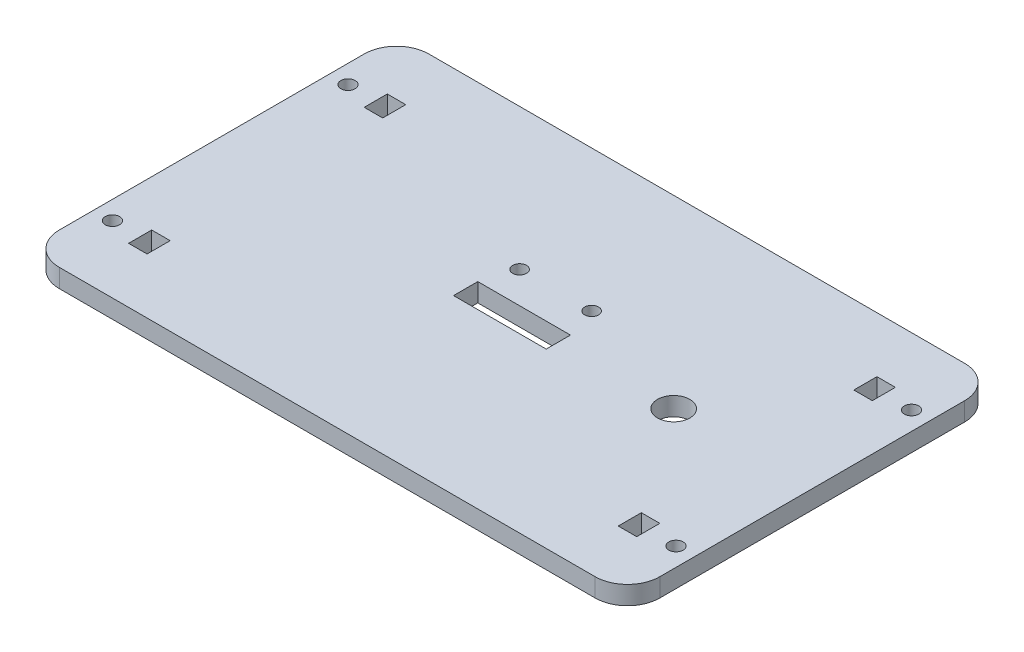
SolidWorks part; units mm, degrees
ref_plane "Front Plane" through (0, 0, 0) normal (0, 0, 1) x (1, 0, 0)
ref_plane "Top Plane" through (0, 0, 0) normal (0, 1, 0) x (1, 0, 0)
ref_plane "Right Plane" through (0, 0, 0) normal (1, 0, 0) x (0, 0, -1)
sketch "Sketch1" plane through (0, 0, 0) normal (0, 1, 0) x (1, 0, 0)
  line L0 (0, 0) -> (0, 18.9717) construction
  line L1 (-58, -40) -> (58, -40)
  line L2 (-65, -33) -> (-65, 33)
  line L3 (-58, 40) -> (58, 40)
  line L4 (65, -33) -> (65, 33)
  line L5 (-65, -40) -> (65, 40) construction
  line L6 (-65, 40) -> (65, -40) construction
  line L11 (0, 0) -> (21.4077, 0) construction
  line L30 (51, -23) -> (55, -23)
  line L31 (51, -23) -> (51, -28)
  line L32 (51, -28) -> (55, -28)
  line L33 (55, -23) -> (55, -28)
  line L34 (51, -23) -> (55, -28) construction
  line L35 (51, -28) -> (55, -23) construction
  line L36 (51, 28) -> (55, 28)
  line L37 (51, 28) -> (51, 23)
  line L38 (51, 23) -> (55, 23)
  line L39 (55, 28) -> (55, 23)
  line L40 (51, 28) -> (55, 23) construction
  line L41 (51, 23) -> (55, 28) construction
  line L42 (-55, 28) -> (-51, 28)
  line L43 (-55, 28) -> (-55, 23)
  line L44 (-55, 23) -> (-51, 23)
  line L45 (-51, 28) -> (-51, 23)
  line L46 (-55, 28) -> (-51, 23) construction
  line L47 (-55, 23) -> (-51, 28) construction
  line L48 (-55, -23) -> (-51, -23)
  line L49 (-55, -23) -> (-55, -28)
  line L50 (-55, -28) -> (-51, -28)
  line L51 (-51, -23) -> (-51, -28)
  line L52 (-55, -23) -> (-51, -28) construction
  line L53 (-55, -28) -> (-51, -23) construction
  line L54 (-10.03, 2.625) -> (10.03, 2.625)
  line L55 (-10.03, 2.625) -> (-10.03, -2.625)
  line L56 (-10.03, -2.625) -> (10.03, -2.625)
  line L57 (10.03, 2.625) -> (10.03, -2.625)
  line L58 (-10.03, 2.625) -> (10.03, -2.625) construction
  line L59 (-10.03, -2.625) -> (10.03, 2.625) construction
  circle A0 centre (61, 25.5) radius 1.55
  circle A1 centre (61, -25.5) radius 1.55
  circle A2 centre (-61, -25.5) radius 1.55
  circle A3 centre (-61, 25.5) radius 1.55
  circle A8 centre (35, 0) radius 3.5
  arc A9 (58, 40) -> (65, 33) centre (58, 33) cw
  arc A10 (58, -40) -> (65, -33) centre (58, -33) ccw
  arc A11 (-58, -40) -> (-65, -33) centre (-58, -33) cw
  arc A12 (-65, 33) -> (-58, 40) centre (-58, 33) cw
  circle A13 centre (-7.8, 9.445) radius 1.5
  circle A14 centre (7.8, 9.445) radius 1.5
  point P0 (0, 0)
  point P6 (53, 25.5)
  point P14 (-53, 25.5)
  point P19 (-53, -25.5)
  point P24 (0, 0)
  point P62 (53, -25.5)
  point P75 (-10.9239, 16.3216)
  point P76 (-8.6491, 16.0183)
  point P77 (-12.3899, 13.4402)
  point P78 (8.7908, 16.3216)
  point P79 (11.2678, 13.4402)
  point P80 (0, 0)
  point P81 (-12.2382, 16.3722)
  point P82 (-5.1, 9.445)
  point P83 (-6.9809, 9.445)
  point P84 (-12.3393, 10.5588)
  dimension "D8" = 3.1
  dimension "D12" = 7
  dimension "D13" = 7
  dimension "D3" = 4
  dimension "D27" = 3
  dimension "D1" = 80
  dimension "D2" = 130
  dimension "D4" = 10
  dimension "D5" = 12
  dimension "D6" = 4
  dimension "D7" = 14.5
  dimension "D9" = 54.97
  dimension "D10" = 54.97
  dimension "D11" = 35
  dimension "D14" = 4
  dimension "D15" = 5
  dimension "D16" = 10
  dimension "D17" = 12
  dimension "D18" = 5
  dimension "D19" = 12
  dimension "D20" = 10
  dimension "D21" = 12
  dimension "D22" = 10
  dimension "D23" = 37.375
  dimension "D24" = 20.06
  dimension "D25" = 5.25
  dimension "D26" = 37.375
  dimension "D29" = 15.6
  dimension "D30" = 8.32
  dimension "D31" = 2.23
  dimension "D32" = 2.23
extrude "Boss-Extrude1" add sketch "Sketch1" along normal blind 4
